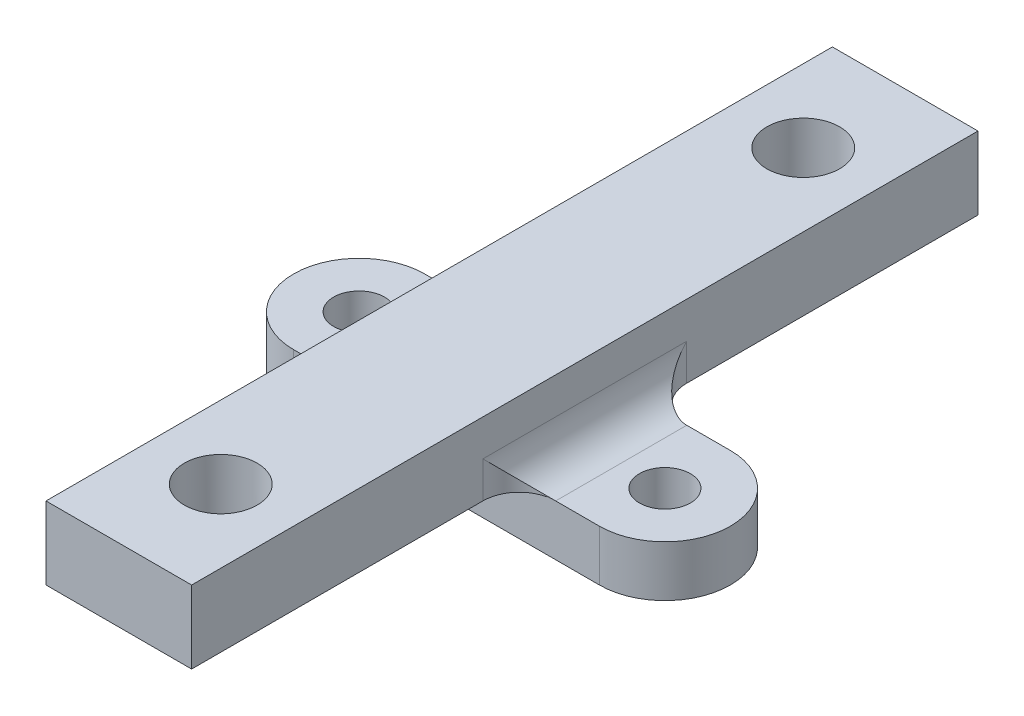
SolidWorks part; units mm, degrees
material "ABS"
ref_plane "Front Plane" through (0, 0, 0) normal (0, 0, 1) x (1, 0, 0)
ref_plane "Top Plane" through (0, 0, 0) normal (0, 1, 0) x (1, 0, 0)
ref_plane "Right Plane" through (0, 0, 0) normal (1, 0, 0) x (0, 0, -1)
sketch "Sketch1" plane through (0, 0, 0) normal (0, 1, 0) x (1, 0, 0)
  line L0 (-21, 9) -> (21, -9) construction
  line L1 (-21, 9) -> (21, 9)
  line L3 (-21, -9) -> (21, -9)
  line L5 (21, 9) -> (-21, -9) construction
  arc A2 (-21, 9) -> (-21, -9) centre (-21, 0) ccw
  arc A3 (21, 9) -> (21, -9) centre (21, 0) cw
  point P0 (0, 0)
  point P8 (30, 0)
  point P9 (-30, 0)
  point P10 (0, 0)
  dimension "D1" = 60
  dimension "D2" = 18
extrude "Boss-Extrude1" add sketch "Sketch1" along normal blind 7
sketch "Sketch2" plane through (0, 0, 0) normal (0, -1, 0) x (1, 0, 0)
  circle A0 centre (-21, 0) radius 3
  dimension "D1" = 6
extrude "Boss-Extrude2" add sketch "Sketch2" along normal blind 1
sketch "Sketch3" plane through (0, 7, 0) normal (0, 1, 0) x (1, 0, 0)
  circle A0 centre (-21, 0) radius 3.5
  dimension "D1" = 7
extrude "Cut-Extrude1" cut sketch "Sketch3" against normal blind 5
sketch "Sketch4" plane through (0, 2, 0) normal (0, 1, 0) x (1, 0, 0)
  circle A0 centre (-21, 0) radius 1.5
  dimension "D1" = 3
extrude "Cut-Extrude2" cut sketch "Sketch4" against normal through all
mirror "Mirror1" about plane through (0, 0, 0) normal (1, 0, 0) of "Boss-Extrude2", "Cut-Extrude2", "Cut-Extrude1"
sketch "Sketch17" plane through (0, 7, 0) normal (0, 1, 0) x (1, 0, 0)
  line L1 (-10, 9) -> (10, 9)
  line L2 (-10, 9) -> (-10, -9)
  line L3 (-10, -9) -> (10, -9)
  line L4 (10, 9) -> (10, -9)
  line L5 (-10, 9) -> (10, -9) construction
  line L6 (-10, -9) -> (10, 9) construction
  line L7 (-21, -9) -> (21, -9) construction
  point P0 (0, 0)
  dimension "D1" = 20
extrude "Boss-Extrude6" add sketch "Sketch17" along normal blind 10
sketch "Sketch18" plane through (0, 0, 9) normal (0, 0, 1) x (1, 0, 0)
  line L1 (-10, 17) -> (10, 17)
  line L2 (-10, 17) -> (-10, 7)
  line L3 (-10, 7) -> (10, 7)
  line L4 (10, 17) -> (10, 7)
extrude "Boss-Extrude7" add sketch "Sketch18" along normal blind 45
mirror "Mirror3" about plane through (0, 0, 0) normal (0, 0, 1) of "Boss-Extrude7"
sketch "Sketch19" plane through (0, 17, 0) normal (0, 1, 0) x (1, 0, 0)
  line L0 (0, -9.9) -> (0, 9.9) construction
  circle A0 centre (0, 40) radius 5
  dimension "D1" = 10
  dimension "D2" = 40
extrude "Cut-Extrude6" cut sketch "Sketch19" against normal up to next contours A0
mirror "Mirror4" about plane through (0, 0, 0) normal (0, 0, 1) of "Cut-Extrude6"
sketch "Sketch14" plane through (0, 7, 0) normal (0, 1, 0) x (1, 0, 0)
  line L0 (-21, 9) -> (21, 9) construction
  line L1 (0, 9) -> (-10, 9)
  line L2 (0, 9) -> (0, -9)
  line L3 (0, -9) -> (-10, -9)
  line L4 (-10, 9) -> (-10, -9)
  line L5 (-21, -9) -> (21, -9) construction
  dimension "D1" = 10
fillet "Fillet4" radius 5 1 edges at (10, 7, 0)
fillet "Fillet6" radius 5 1 edges at (-10, 7, 0)
fillet "Fillet8" radius 5 4 edges at (-10, 9.5, 9) (-10, 9.5, -9) (10, 9.5, -9) (10, 9.5, 9)
